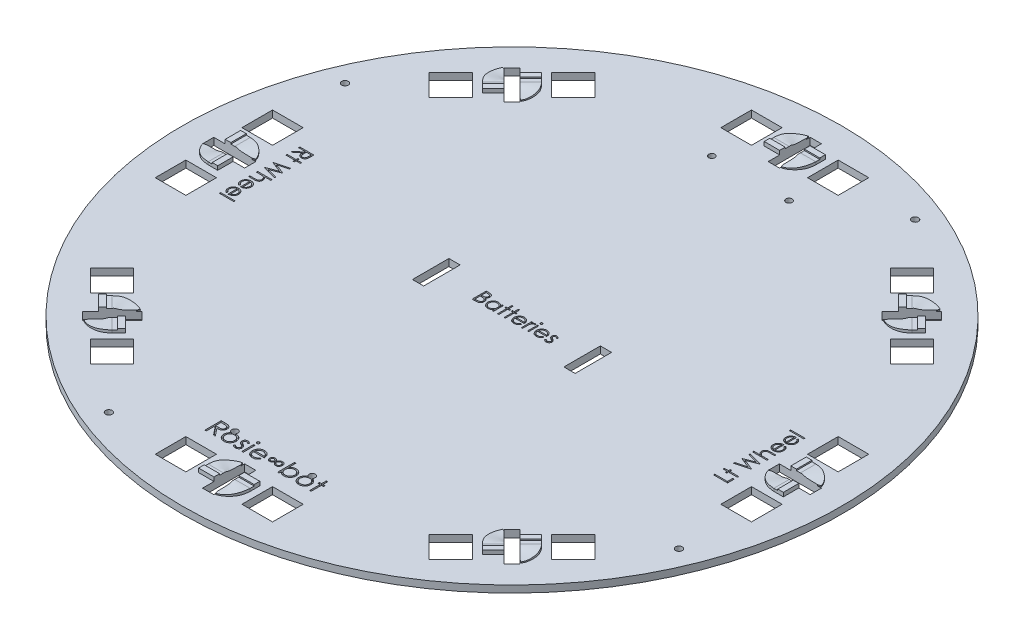
SolidWorks part; units mm, degrees
other "DetailItem1"
ref_plane "Front" through (0, 0, 0) normal (0, 0, 1) x (1, 0, 0)
ref_plane "Top" through (0, 0, 0) normal (0, 1, 0) x (1, 0, 0)
ref_plane "Right" through (0, 0, 0) normal (1, 0, 0) x (0, 0, -1)
sketch "Sketch1" plane through (0, 0, 0) normal (0, 1, 0) x (1, 0, 0)
  circle A0 centre (0, 0) radius 149.225
  dimension "D1" = 298.45
extrude "Boss-Extrude1" add sketch "Sketch1" along normal blind 3.175 contours A0
sketch "Sketch2" plane through (0, 3.175, 0) normal (0, 1, 0) x (1, 0, 0)
  line L1 (-2.54, -137.5833) -> (2.54, -137.5833)
  line L2 (-2.54, -137.5833) -> (-2.54, -118.5333)
  line L3 (-2.54, -118.5333) -> (2.54, -118.5333)
  line L4 (2.54, -137.5833) -> (2.54, -118.5333)
  circle A0 centre (0, 0) radius 149.225 construction
  point P4 (0, -118.5333)
  dimension "D1" = 5.08
  dimension "D2" = 19.05
  dimension "D3" = 137.5833
extrude "Cut-Extrude1" cut sketch "Sketch2" against normal up to next and the other way through all contours L1 L4 L3 L2
sketch "Sketch4" plane through (0, 3.175, 0) normal (0, 1, 0) x (1, 0, 0)
  line L0 (0, -128.0583) -> (-2.9434, -118.9995) construction
  line L1 (-2.9434, -118.9995) -> (0, -128.0583) construction
  line L2 (0, -128.0583) -> (-5.5987, -120.3525) construction
  line L3 (0, -128.0583) -> (-7.7059, -122.4597) construction
  line L4 (0, -128.0583) -> (-9.0588, -125.115) construction
  line L5 (0, -128.0583) -> (-9.525, -128.0583) construction
  line L9 (2.54, -118.5333) -> (-2.54, -118.5333) construction
  line L10 (2.54, -118.5333) -> (2.54, -137.5833) construction
  line L11 (-2.54, -118.5333) -> (-2.54, -137.5833) construction
  line L12 (2.54, -137.5833) -> (-2.54, -137.5833) construction
  circle A0 centre (0, -128.0583) radius 9.525 construction
  point P16 (0, -118.5333)
  point P19 (2.54, -128.0583)
  dimension "D1" = 18
  dimension "D2" = 18
  dimension "D3" = 18
  dimension "D4" = 18
  dimension "D5" = 18
ref_plane "Plane1" through (-37.6354, 0, 12.2285) normal (0.9511, 0, -0.309) x (-0.309, 0, -0.9511)
ref_plane "Plane2" through (-60.8954, 0, 44.2431) normal (0.809, 0, -0.5878) x (-0.5878, 0, -0.809)
ref_plane "Plane3" through (-60.8954, 0, 83.8153) normal (0.5878, 0, -0.809) x (-0.809, 0, -0.5878)
ref_plane "Plane4" through (-37.6354, 0, 115.8299) normal (0.309, 0, -0.9511) x (-0.9511, 0, -0.309)
ref_plane "Plane5" through (0, 0, 128.0583) normal (0, 0, -1) x (-1, 0, 0)
sketch "Sketch5" plane through (-37.6354, 0, 12.2285) normal (0.9511, 0, -0.309) x (-0.309, 0, -0.9511)
  line L0 (-111.947, 3.175) -> (-130.0646, 3.175) construction
  line L1 (-113.5711, 3.175) -> (-112.2657, 3.175)
  line L2 (-113.5711, 3.175) -> (-113.5711, 3.683)
  line L3 (-113.5711, 3.683) -> (-112.2657, 3.683)
  line L4 (-112.2657, 3.175) -> (-112.2657, 3.683)
  dimension "D2" = 0.508
sketch "Sketch6" plane through (-60.8954, 0, 44.2431) normal (0.809, 0, -0.5878) x (-0.5878, 0, -0.809)
  line L0 (-94.4025, 3.175) -> (-109.8143, 3.175) construction
  line L1 (-99.2801, 3.175) -> (-94.0764, 3.175)
  line L2 (-99.2801, 3.175) -> (-99.2801, 3.775)
  line L3 (-99.2801, 3.775) -> (-94.0764, 3.775)
  line L4 (-94.0764, 3.175) -> (-94.0764, 3.775)
  dimension "D2" = 0.6
sketch "Sketch7" plane through (-60.8954, 0, 83.8153) normal (0.5878, 0, -0.809) x (-0.809, 0, -0.5878)
  line L0 (-67.6172, 3.175) -> (-78.8146, 3.175) construction
  line L1 (-72.1312, 3.175) -> (-65.7458, 3.175)
  line L2 (-72.1312, 3.175) -> (-72.1312, 4.075)
  line L3 (-72.1312, 4.075) -> (-65.7458, 4.075)
  line L4 (-65.7458, 3.175) -> (-65.7458, 4.075)
  dimension "D2" = 0.9
sketch "Sketch10" plane through (-37.6354, 0, 115.8299) normal (0.309, 0, -0.9511) x (-0.9511, 0, -0.309)
  line L0 (-39.5722, 3.175) -> (-30.5134, 3.175) construction
  line L1 (-36.9015, 3.175) -> (-30.0472, 3.175)
  line L2 (-36.9015, 3.175) -> (-36.9015, 4.375)
  line L3 (-36.9015, 4.375) -> (-30.0472, 4.375)
  line L4 (-30.0472, 3.175) -> (-30.0472, 4.375)
  dimension "D3" = 1.2
sketch "Sketch11" plane through (0, 0, 128.0583) normal (0, 0, -1) x (-1, 0, 0)
  line L0 (0, 3.175) -> (9.525, 3.175) construction
  line L1 (2.54, 3.175) -> (9.525, 3.175)
  line L2 (2.54, 3.175) -> (2.54, 4.375)
  line L3 (2.54, 4.375) -> (9.525, 4.375)
  line L4 (9.525, 3.175) -> (9.525, 4.375)
  dimension "D3" = 1.2
loft "Loft1" add profiles "Sketch5", "Sketch6", "Sketch7", "Sketch10", "Sketch11" connector at (-2.54, 3.683, 120.241) connector at (-2.54, 3.775, 124.5623) connector at (-2.54, 4.075, 126.2129) connector at (-2.54, 4.375, 127.233) connector at (-2.54, 4.375, 128.0583)
sketch "Sketch13" plane through (-104.9799, 0, 128.0583) normal (0, 0, -1) x (-1, 0, 0)
  line L6 (-95.4549, 3.175) -> (-102.4399, 3.175)
  line L7 (-95.4549, 3.175) -> (-95.4549, 4.375)
  line L8 (-95.4549, 4.375) -> (-102.4399, 4.375)
  line L9 (-102.4399, 3.175) -> (-102.4399, 4.375)
extrude "Boss-Extrude4" add sketch "Sketch13" against normal blind 1.7907
sketch "Sketch25" plane through (0, 0, 129.849) normal (0, 0, 1) x (1, 0, 0)
  line L0 (-9.525, 4.375) -> (-2.54, 4.375) construction
  line L1 (-9.525, 3.175) -> (-2.54, 3.175)
  line L2 (-9.525, 3.175) -> (-9.525, 4.975)
  line L3 (-9.525, 4.975) -> (-2.54, 4.975)
  line L4 (-2.54, 3.175) -> (-2.54, 4.975)
  dimension "D1" = 0.6
extrude "Boss-Extrude5" add sketch "Sketch25" along normal blind 2.54
sketch "Sketch14" plane through (-2.54, 0, 0) normal (1, 0, 0) x (0, 0, -1)
  line L0 (-128.0583, 3.175) -> (-128.0583, 0) construction
  line L1 (-118.5333, 0) -> (-137.5833, 0) construction
ref_plane "Plane6" through (0, 0, 0) normal (1, 0, 0) x (0, 0, -1)
sketch "Sketch15" plane through (0, 0, 0) normal (1, 0, 0) x (0, 0, -1)
  line L0 (-128.0583, 0) -> (-128.0583, 3.175) construction
pattern_circular "CirPattern1" count 2 over 360 about axis through (0, 0, 128.0583) along (0, 1, 0) of "Loft1", "Boss-Extrude5", "Boss-Extrude4" reverse direction yes
ref_axis "Axis1" through (0, 50, 0) along (0, -1, 0)
pattern_circular "CirPattern5" count 8 over 360 about axis through (0, 50, 0) along (0, -1, 0) of "CirPattern1", "Cut-Extrude1"
sketch "Sketch18" plane through (0, 3.175, 0) normal (0, 1, 0) x (1, 0, 0)
  line L4 (0, -149.225) -> (0, 149.225) construction
  line L5 (0, -1.7463) -> (0, 1.7463) construction
  line L6 (-149.225, 0) -> (149.225, 0) construction
  circle A8 centre (0, 0) radius 149.225 construction
sketch "Sketch19" plane through (0, 3.175, 0) normal (0, 1, 0) x (1, 0, 0)
  line L0 (-53.4609, -129.066) -> (0, 0) construction
  line L1 (0, -149.225) -> (0, 149.225) construction
  circle A1 centre (-53.4609, -129.066) radius 1.5
  dimension "D1" = 139.7
  dimension "D4" = 3
  dimension "D5" = 22.5
extrude "Cut-Extrude2" cut sketch "Sketch19" against normal through all
pattern_circular "CirPattern7" count 4 over 360 about axis through (0, 50, 0) along (0, -1, 0) of "Cut-Extrude2"
sketch "Sketch23" plane through (0, 3.175, 0) normal (0, 1, 0) x (1, 0, 0)
  line L9 (-2.54, -132.389) -> (-2.54, -137.5833) construction
  line L10 (-26.5557, -121.1305) -> (-12.7, -121.1305)
  line L11 (-26.5557, -121.1305) -> (-26.5557, -134.9862)
  line L16 (-26.5557, -134.9862) -> (-12.7, -134.9862)
  line L17 (-12.7, -121.1305) -> (-12.7, -134.9862)
  line L19 (2.54, -118.5333) -> (2.54, -123.7276) construction
  line L20 (0, -50) -> (0, 50) construction
  line L21 (12.7, -121.1305) -> (12.7, -134.9862)
  line L22 (26.5557, -134.9862) -> (12.7, -134.9862)
  line L23 (26.5557, -121.1305) -> (26.5557, -134.9862)
  line L24 (26.5557, -121.1305) -> (12.7, -121.1305)
  point P8 (-2.54, -134.9862)
  point P9 (2.54, -121.1305)
  dimension "D2" = 10.16
extrude "Cut-Extrude6" cut sketch "Sketch23" against normal through all
pattern_circular "CirPattern8" count 8 over 360 about axis through (0, 50, 0) along (0, -1, 0) of "Cut-Extrude6"
sketch "Sketch16" plane through (0, 3.175, 0) normal (0, 1, 0) x (1, 0, 0)
  line L1 (-16.4163, -2.4279) -> (16.4163, -2.4279) construction
  line L2 (0, -149.225) -> (0, 149.225) construction
  line L3 (-114.3, 19.05) -> (-114.3, -19.05) construction
  line L4 (-149.225, 0) -> (149.225, 0) construction
  line L5 (114.3, 19.05) -> (114.3, -19.05) construction
  line L6 (-25.719, -114.3) -> (25.719, -114.3) construction
  circle A2 centre (0, 0) radius 114.3 construction
  text T0 "Rosie∞bot\r\n" font "Century Gothic" height in points 28
  text T1 "Batteries"
  text T2 "Rt Wheel\r\n"
  text T3 "Lt Wheel"
  point P4 (-114.3, 0)
  point P7 (0, -114.3)
  point P10 (0, -2.4279)
  point P15 (114.3, 0)
  dimension "D7" = 228.6
  dimension "D1" = 32.8326
  dimension "D2" = 38.1
  dimension "D3" = 51.438
extrude "Cut-Extrude4" cut sketch "Sketch16" against normal blind 1.27
sketch "Sketch26" plane through (0, 3.175, 0) normal (0, 1, 0) x (1, 0, 0)
  line L0 (-149.225, 0) -> (149.225, 0) construction
  line L1 (-36.83, 8.255) -> (-31.75, 8.255)
  line L2 (-36.83, 8.255) -> (-36.83, -8.255)
  line L3 (-36.83, -8.255) -> (-31.75, -8.255)
  line L4 (-31.75, 8.255) -> (-31.75, -8.255)
  line L5 (0, -149.225) -> (0, 149.225) construction
  point P4 (-36.83, 0)
  dimension "D1" = 16.51
  dimension "D2" = 5.08
  dimension "D3" = 31.75
extrude "Cut-Extrude7" cut sketch "Sketch26" against normal through all
mirror "Mirror1" about plane through (0, 0, 0) normal (1, 0, 0) of "Cut-Extrude7"
sketch "Sketch27" plane through (0, 0, 0) normal (0, -1, 0) x (1, 0, 0)
  line L0 (0, 149.225) -> (0, -149.225) construction
  line L1 (-149.225, 0) -> (149.225, 0) construction
  circle A0 centre (-17.5, -107.95) radius 1.4
  dimension "D3" = 2.8
  dimension "D1" = 17.5
  dimension "D2" = 107.95
extrude "Cut-Extrude8" cut sketch "Sketch27" against normal through all both and the other way through all
mirror "Mirror2" about plane through (0, 0, 0) normal (1, 0, 0) of "Cut-Extrude8"
mirror "Mirror3" about plane through (0, 0, 0) normal (0, 0, 1) of "Mirror2"
sketch "Sketch28" plane through (0, 0, 0) normal (0, -1, 0) x (-1, 0, 0)
  line L0 (19.05, 101.6) -> (-19.05, 101.6) construction
  line L1 (0, -149.225) -> (0, 149.225) construction
  line L2 (149.225, 0) -> (-149.225, 0) construction
  line L3 (19.05, -101.6) -> (-19.05, -101.6) construction
  text T0 "Bk Caster"
  text T1 "Ft Caster"
  point P2 (0, 101.6)
  point P6 (0, -101.6)
  dimension "D1" = 101.6
  dimension "D2" = 38.1
  dimension "D3" = 101.6
extrude "Cut-Extrude9" cut sketch "Sketch28" against normal blind 1.27
